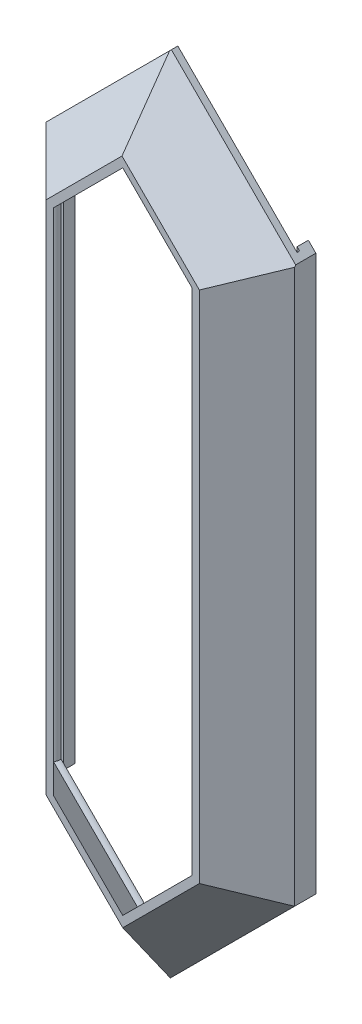
SolidWorks part; units mm, degrees
ref_plane "Спереди" through (0, 0, 0) normal (0, 0, 1) x (1, 0, 0)
ref_plane "Сверху" through (0, 0, 0) normal (0, 1, 0) x (1, 0, 0)
ref_plane "Справа" through (0, 0, 0) normal (1, 0, 0) x (0, 0, -1)
sketch "Skizze1" plane through (0, 0, 0) normal (0, 0, 1) x (1, 0, 0)
  line L0 (-19.8343, 44.1) -> (0, 63.9343)
  line L1 (0, 63.9343) -> (19.8343, 44.1)
  line L2 (19.8343, 44.1) -> (19.8343, -44.5)
  line L3 (19.8343, -44.5) -> (0, -64.3343)
  line L4 (0, -64.3343) -> (-19.8343, -44.5)
  line L5 (-19.8343, -44.5) -> (-19.8343, 44.1)
  line L6 (0, -64.3343) -> (0, 76.8777) construction
  line L7 (-19.8343, -44.5) -> (59.503, -44.5) construction
  dimension "D1" = 90
  dimension "D2" = 88.6
  dimension "D3" = 28.05
  dimension "D4" = 90
  dimension "D5" = 44.5
extrude "Бобышка-Вытянуть2" add sketch "Skizze1" along normal blind 8
sketch "Эскиз1" plane through (0, 0, 0) normal (0, 0, -1) x (-1, 0, 0)
  line L0 (0, 62.803) -> (19.0343, 43.7686)
  line L1 (19.0343, 43.7686) -> (19.0343, -44.1686)
  line L2 (19.0343, -44.1686) -> (0, -63.203)
  line L3 (0, -63.203) -> (-19.0343, -44.1686)
  line L4 (-19.0343, -44.1686) -> (-19.0343, 43.7686)
  line L5 (-19.0343, 43.7686) -> (0, 62.803)
  line L6 (0, 63.9343) -> (19.8343, 44.1) construction
  line L7 (-19.8343, 44.1) -> (0, 63.9343) construction
  line L8 (-19.8343, -44.5) -> (-19.8343, 44.1) construction
  line L9 (19.8343, 44.1) -> (19.8343, -44.5) construction
  line L10 (19.8343, -44.5) -> (0, -64.3343) construction
  line L11 (0, -64.3343) -> (-19.8343, -44.5) construction
  dimension "D1" = 0.8
  dimension "D2" = 0.8
  dimension "D3" = 0.8
  dimension "D4" = 0.8
  dimension "D5" = 0.8
  dimension "D6" = 0.8
extrude "Вырез-Вытянуть1" cut sketch "Эскиз1" against normal blind 8 draft 45
sketch "Эскиз3" plane through (0, 0, 8) normal (0, 0, 1) x (1, 0, 0)
  line L0 (-12.2343, 40.952) -> (-0.1201, 53.0662)
  line L1 (-0.1201, 53.0662) -> (12.2343, 40.7118)
  line L2 (12.2343, 40.7118) -> (12.2343, -41.352)
  line L3 (12.2343, -41.352) -> (0, -53.5863)
  line L4 (0, -53.5863) -> (-12.2343, -41.352)
  line L5 (-12.2343, -41.352) -> (-12.2343, 40.952)
  line L6 (-11.0343, 40.4549) -> (0, 51.4893) construction
  line L7 (0, 51.4893) -> (11.0343, 40.4549) construction
  line L8 (11.0343, 40.4549) -> (11.0343, -40.8549) construction
  line L9 (-11.0343, -40.8549) -> (-11.0343, 40.4549) construction
  line L11 (11.0343, -40.8549) -> (0, -51.8893) construction
  line L12 (0, -51.8893) -> (-11.0343, -40.8549) construction
  dimension "D1" = 1.2
  dimension "D2" = 1.2
  dimension "D3" = 1.2
  dimension "D4" = 1.2
  dimension "D5" = 1.0302
  dimension "D6" = 1.2
extrude "Вырез-Вытянуть5" cut sketch "Эскиз3" against normal blind 8 draft 45 flip side to cut
sketch "Эскиз4" plane through (0, 0, 0) normal (0, 0, -1) x (-1, 0, 0)
  line L0 (0, -64.3343) -> (-19.8343, -44.5) construction
  line L1 (19.8343, -44.5) -> (0, -64.3343) construction
  line L2 (-19.8343, -44.5) -> (-19.8343, 44.1) construction
  line L3 (-19.8343, 44.1) -> (0, 63.9343) construction
  line L4 (19.8343, 44.1) -> (19.8343, -44.5) construction
  line L5 (0, 63.9343) -> (19.8343, 44.1) construction
  line L6 (0, -64.3343) -> (-19.8343, -44.5)
  line L7 (19.8343, -44.5) -> (0, -64.3343)
  line L8 (-19.8343, -44.5) -> (-19.8343, 44.1)
  line L9 (-19.8343, 44.1) -> (0, 63.9343)
  line L10 (19.8343, 44.1) -> (19.8343, -44.5)
  line L11 (0, 63.9343) -> (19.8343, 44.1)
extrude "Вытянуть-Тонкостенный1" add sketch "Эскиз4" along normal blind 3 thin thin type one direction reverse wall 1.2
fillet "Скругление1" radius 1 2 edges at (-9.3172, 52.9201, 0) (-18.6343, -0.2, 0)
fillet "Скругление2" radius 1 4 edges at (-9.5172, -53.1201, 0) (9.3172, -53.3201, 0) (18.6343, -0.2, 0) (9.1758, 53.0615, 0)
sketch "Эскиз5" plane through (18.6343, 0, 0) normal (-1, 0, 0) x (0, 0, 1)
  line L0 (-3, 43.6029) -> (-0.8, 43.6029) construction
  line L1 (-1.2, 43.6029) -> (-0.8, 43.6029)
  line L2 (-1.2, 43.6029) -> (-1.2, -44.0029)
  line L3 (-1.2, -44.0029) -> (-0.8, -44.0029)
  line L4 (-0.8, 43.6029) -> (-0.8, -44.0029)
  line L5 (-3, -44.0029) -> (-0.8, -44.0029) construction
  line L7 (-3, 43.6029) -> (-3, -44.0029) construction
  dimension "D1" = 0.4
  dimension "D2" = 1.8
extrude "Вырез-Вытянуть6" cut sketch "Эскиз5" against normal blind 0.4 and the other way blind 37.9
sketch "Эскиз7" plane through (0, 0, -0.8) normal (0, 0, -1) x (-1, 0, 0)
  line L0 (19.2657, -44.0029) -> (19.2657, 43.6029) construction
  line L1 (-19.0343, 43.6029) -> (19.2657, 43.6029)
  line L2 (-19.0343, 43.6029) -> (-19.0343, 66.5049)
  line L3 (-19.0343, 66.5049) -> (19.2657, 66.5049)
  line L4 (19.2657, 43.6029) -> (19.2657, 66.5049)
  line L5 (19.2657, 43.6029) -> (18.6343, 43.6029) construction
extrude "Вырез-Вытянуть8" cut sketch "Эскиз7" along normal blind 0.4
sketch "Эскиз8" plane through (0, 0, -0.8) normal (0, 0, -1) x (-1, 0, 0)
  line L0 (19.2657, -44.0029) -> (19.2657, 44.6687) construction
  line L1 (-19.0343, -44.0029) -> (19.2657, -44.0029)
  line L2 (-19.0343, -44.0029) -> (-19.0343, -69.5742)
  line L3 (-19.0343, -69.5742) -> (19.2657, -69.5742)
  line L4 (19.2657, -44.0029) -> (19.2657, -69.5742)
extrude "Вырез-Вытянуть9" cut sketch "Эскиз8" along normal blind 0.4
sketch "Эскиз9" plane through (0, 0, -3) normal (0, 0, -1) x (-1, 0, 0)
  line L0 (18.6343, -44.0029) -> (18.6343, 43.6029) construction
  line L1 (18.6343, 68.6855) -> (-18.6343, 68.6855)
  line L2 (18.6343, 68.6855) -> (18.6343, -67.4756)
  line L3 (18.6343, -67.4756) -> (-18.6343, -67.4756)
  line L4 (-18.6343, 68.6855) -> (-18.6343, -67.4756)
  line L5 (-18.6343, 43.6029) -> (-18.6343, -44.0029) construction
  point P4 (-9.9172, -67.4756)
  dimension "D1" = 0
  dimension "D2" = 0
extrude "Вырез-Вытянуть10" cut sketch "Эскиз9" against normal blind 1.8
